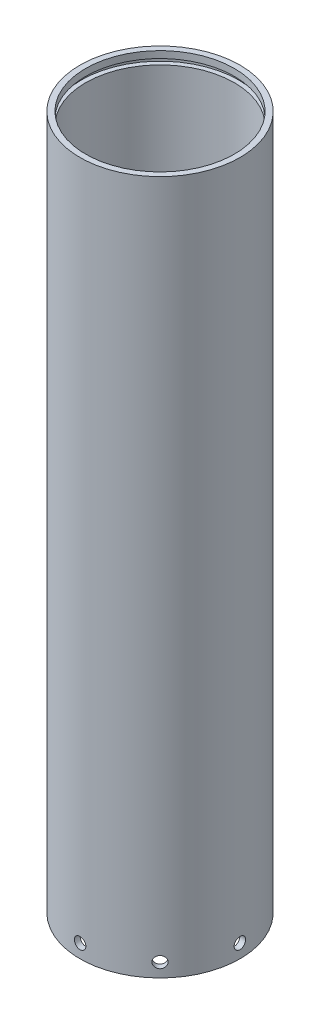
SolidWorks part; units mm, degrees
material "1060 Alloy"
ref_plane "Front Plane" through (0, 0, 0) normal (0, 0, 1) x (1, 0, 0)
ref_plane "Top Plane" through (0, 0, 0) normal (0, 1, 0) x (1, 0, 0)
ref_plane "Right Plane" through (0, 0, 0) normal (1, 0, 0) x (0, 0, -1)
sketch "Sketch2" plane through (0, 0, 0) normal (0, 0, 1) x (1, 0, 0)
  line L0 (0, 0) -> (0, 365.76) construction
  line L3 (41.275, 0) -> (44.45, 0)
  line L5 (41.275, 385.3815) -> (44.45, 385.3815)
  line L6 (44.45, 0) -> (44.45, 385.3815)
  line L11 (41.275, 385.3815) -> (41.275, 192.6907)
  line L12 (41.275, 192.6907) -> (41.2565, 192.6651)
  line L13 (41.275, 192.6907) -> (41.275, 0)
  line L14 (0, -55) -> (0, 55) construction
  dimension "D3" = 3.175
  dimension "D4" = 385.3815
revolve "Revolve1" add sketch "Sketch2" angle 360 about L0 region at (42.8625, 192.6908, 0)
ref_axis "Axis1" through (0, -17.0472, 0) along (0, 1, 0)
ref_plane "Plane1" through (0, 7.62, 0) normal (0, -1, 0) x (-1, 0, 0)
ref_axis "Axis2" through (0, 7.62, 88.99) along (0, 0, -1)
hole_wizard "1/4 (0.25) Diameter Hole1" positions "3DSketch1" profile "Sketch3" hole size "1/4" standard "ANSI Inch" end condition up to next
sketch3d "3DSketch1"
  line L0 (0, 7.62, 88.99) -> (0, 7.62, -88.99) construction
  point P0 (0, 7.62, -44.45)
sketch "Sketch3" plane through (0, 7.62, -44.45) normal (1, 0, 0) x (0, 1, 0)
  line L0 (0, 0) -> (0, 3.175)
  line L1 (0, 3.175) -> (3.175, 3.175)
  line L2 (3.175, 3.175) -> (3.175, 0)
  line L5 (3.175, 0) -> (0, 0)
  line L11 (0, -6.35) -> (0, 107.95) construction
  dimension "Thru Hole Dia." = 6.35
  dimension "Thru Hole Depth" = 3.175
pattern_circular "CirPattern1" count 8 over 360 about axis through (0, -17.0472, 0) along (0, 1, 0) of "1/4 (0.25) Diameter Hole1"
ref_plane "Plane2" through (0, 381.5715, 0) normal (0, 1, 0) x (1, 0, 0)
ref_axis "Axis3" through (0, 381.5715, -48.895) along (0, 0, 1)
sketch "Sketch4" plane through (0, 0, 0) normal (0, 0, 1) x (1, 0, 0)
  line L0 (0, -17.0472) -> (0, 357.9914) construction
  line L1 (0, 381.5715) -> (-43.7642, 381.5715)
  line L2 (0, 381.5715) -> (0, 378.5235)
  line L3 (0, 378.5235) -> (-43.7642, 378.5235)
  line L4 (-43.7642, 381.5715) -> (-43.7642, 378.5235)
  line L5 (48.895, 381.5715) -> (-48.895, 381.5715) construction
  dimension "D1" = 43.7642
  dimension "D2" = 3.048
revolve "Cut-Revolve2" cut sketch "Sketch4" angle 360 about axis through (0, -17.0472, 0) along (0, 1, 0)
